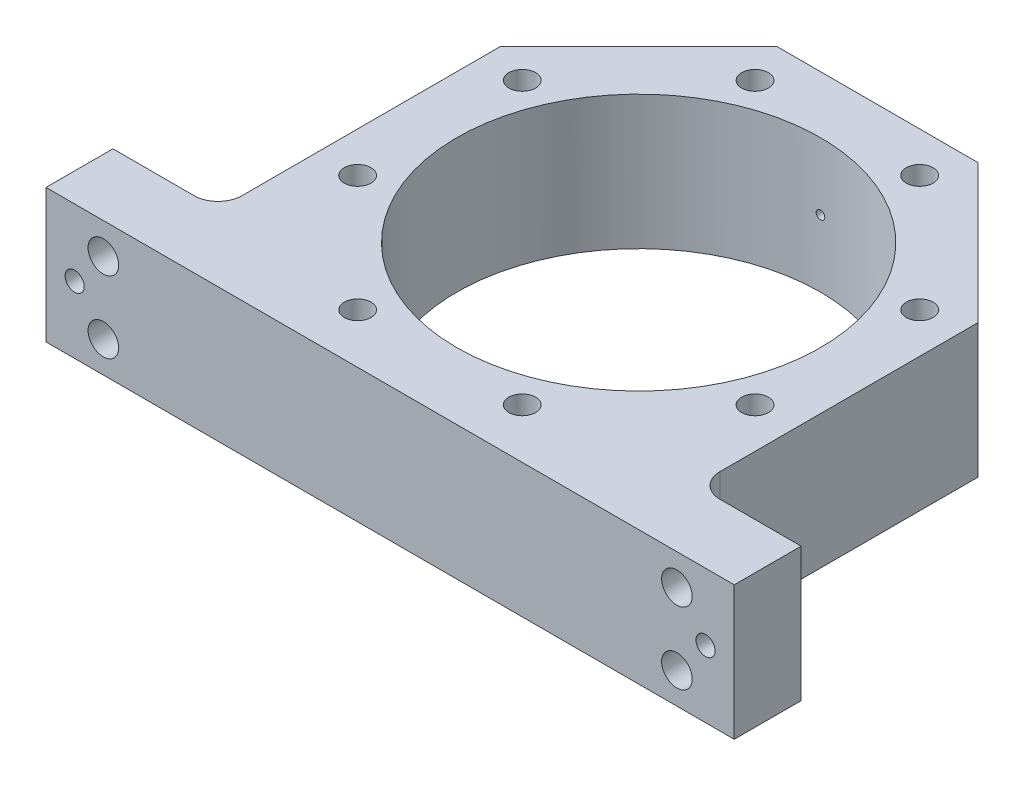
SolidWorks part; units mm, degrees
ref_plane "前视基准面" through (0, 0, 0) normal (0, 0, 1) x (1, 0, 0)
ref_plane "上视基准面" through (0, 0, 0) normal (0, 1, 0) x (1, 0, 0)
ref_plane "右视基准面" through (0, 0, 0) normal (1, 0, 0) x (0, 0, -1)
sketch "草图1" plane through (0, 0, 0) normal (0, 1, 0) x (1, 0, 0)
  line L0 (0, 0) -> (0, 453.125) construction
  line L1 (360, 0) -> (-360, 0)
  line L2 (-360, 0) -> (-360, 70)
  line L3 (-360, 70) -> (-250, 70)
  line L4 (-250, 70) -> (-250, 365)
  line L5 (-250, 365) -> (-105, 510)
  line L6 (-105, 510) -> (105, 510)
  line L8 (250, 365) -> (105, 510)
  line L9 (360, 0) -> (360, 70)
  line L10 (360, 70) -> (250, 70)
  line L11 (250, 70) -> (250, 365)
  point P6 (0, 0)
  point P15 (0, 510)
  dimension "D1" = 500
  dimension "D2" = 720
  dimension "D3" = 70
  dimension "D4" = 510
  dimension "D5" = 145
  dimension "D6" = 145
extrude "凸台-拉伸1" add sketch "草图1" along normal blind 140
sketch "草图2" plane through (0, 140, 0) normal (0, 1, 0) x (1, 0, 0)
  line L0 (0, 0) -> (0, 541.2586) construction
  line L1 (-360, 0) -> (360, 0) construction
  circle A0 centre (0, 260) radius 190.25
  point P5 (0, 0)
  dimension "D1" = 380.5
  dimension "D2" = 260
extrude "切除-拉伸1" cut sketch "草图2" against normal up to next
sketch "草图3" plane through (0, 140, 0) normal (0, 1, 0) x (1, 0, 0)
  line L0 (-86.1038, 467.8729) -> (0, 260) construction
  line L1 (0, 260) -> (0, 535.0515) construction
  circle A0 centre (0, 260) radius 225 construction
  circle A1 centre (-86.1038, 467.8729) radius 14
  point P6 (-86.8919, 469.7756)
  dimension "D1" = 28
  dimension "D3" = 450
  dimension "D2" = 22.5
extrude "切除-拉伸2" cut sketch "草图3" against normal blind 35
pattern_circular "阵列(圆周)1" count 8 over 360 about axis through (0, -0.001, -260) along (0, 1, 0) of "切除-拉伸2"
ref_plane "基准面1" through (0, 70, 0) normal (0, 1, 0) x (1, 0, 0)
mirror "镜向1" about plane through (0, 70, 0) normal (0, 1, 0) of "阵列(圆周)1"
sketch "草图4" plane through (0, 0, -510) normal (0, 0, -1) x (-1, 0, 0)
  line L0 (0, 140) -> (0, 0) construction
  line L1 (-105, 140) -> (105, 140) construction
  line L2 (-105, 70) -> (105, 70) construction
  line L3 (-105, 140) -> (-105, 0) construction
  line L4 (105, 140) -> (105, 0) construction
  circle A0 centre (0, 70) radius 4.25
  dimension "D1" = 8.5
extrude "切除-拉伸3" cut sketch "草图4" against normal blind 15
sketch "草图6" plane through (0, 0, -510) normal (0, 0, -1) x (-1, 0, 0)
  circle A0 centre (0, 70) radius 4.5
  dimension "D1" = 9
extrude "切除-拉伸4" cut sketch "草图6" against normal up to next from offset 15 offset against normal yes
sketch "草图7" plane through (0, 0, -70) normal (0, 0, -1) x (-1, 0, 0)
  line L0 (-360, 70) -> (360, 70) construction
  line L1 (-360, 140) -> (-360, 0) construction
  line L2 (360, 140) -> (360, 0) construction
  line L3 (0, 0) -> (0, 140) construction
  line L4 (-105, 140) -> (105, 140) construction
  circle A0 centre (-300, 107.5) radius 16
  circle A1 centre (-330, 70) radius 10
  dimension "D1" = 32
  dimension "D2" = 20
  dimension "D3" = 75
  dimension "D4" = 600
  dimension "D5" = 660
extrude "切除-拉伸5" cut sketch "草图7" against normal up to next contours A0 region at (300, 107.5, -70)
sketch "草图8" plane through (0, 0, -70) normal (0, 0, -1) x (-1, 0, 0)
  circle A0 centre (-300, 107.5) radius 24
extrude "切除-拉伸6" cut sketch "草图8" against normal blind 30
pattern_linear "阵列(线性)1" count 2 spacing 600 along (-1, 0, 0) count 2 spacing 75 along (0, -1, 0) of "切除-拉伸6", "切除-拉伸5"
extrude "切除-拉伸7" cut sketch "草图7<3>" against normal up to next contours A1
sketch "草图7<3>" plane through (0, 0, -70) normal (0, 0, -1) x (-1, 0, 0) same geometry as "草图7"
pattern_linear "阵列(线性)2" count 2 spacing 660 along (-1, 0, 0) of "切除-拉伸7"
fillet "圆角1" radius 25 2 edges at (-250, 70, -70) (250, 70, -70)
